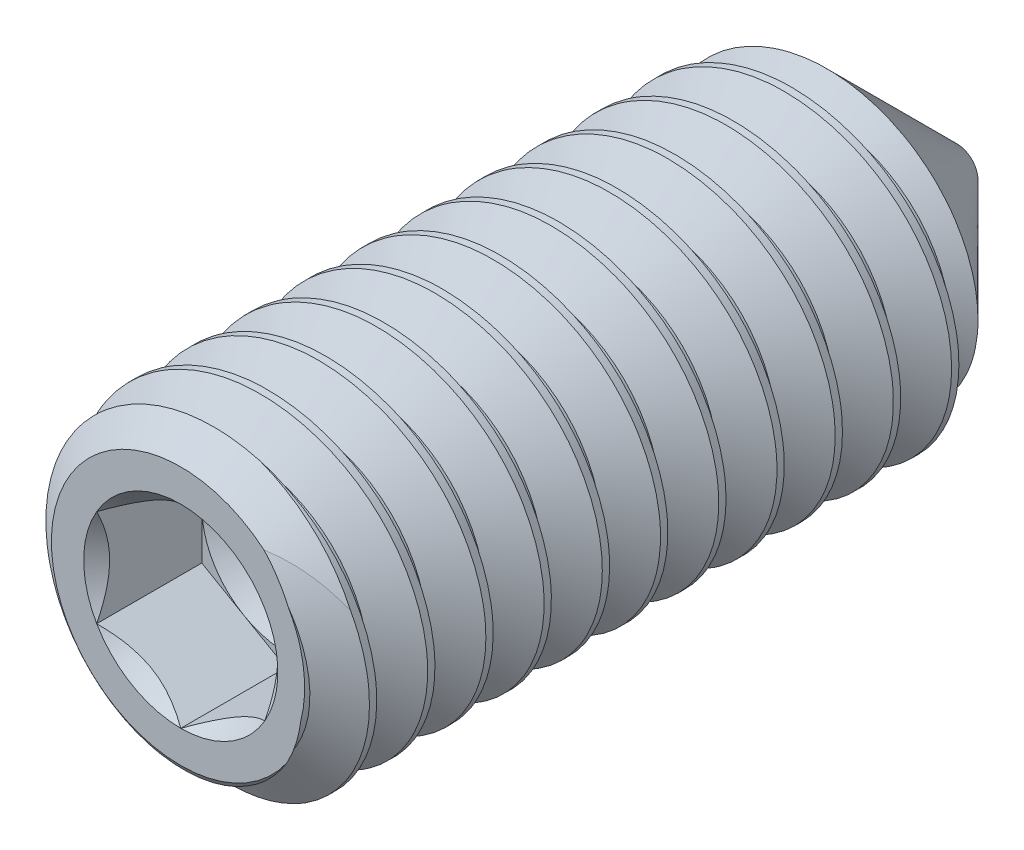
SolidWorks part; units mm, degrees
ref_plane "Front" through (0, 0, 0) normal (0, 0, 1) x (1, 0, 0)
ref_plane "Top" through (0, 0, 0) normal (0, 1, 0) x (1, 0, 0)
ref_plane "Right" through (0, 0, 0) normal (1, 0, 0) x (0, 0, -1)
sketch "Body Sketch" plane through (0, 0, 0) normal (1, 0, 0) x (0, 0, -1)
  line L0 (-3, 0) -> (-3, 1)
  line L1 (-3, 1) -> (-2.8249, 1.25)
  line L2 (-2.8249, 1.25) -> (1.9125, 1.25)
  line L3 (1.9125, 1.25) -> (3, 0.1625)
  line L4 (-3, 1) -> (-3, -1) construction
  line L5 (3, 0) -> (-3, 0)
  line L6 (0, 1.25) -> (0, -1.25) construction
  line L8 (3, 0.1625) -> (3, 0)
  line L9 (-3, -1.25) -> (3, -1.25) construction
  line L10 (3, 0.1625) -> (3, -0.1625) construction
  line L11 (3, -0.1625) -> (1.9125, -1.25) construction
  line L13 (3, 0.1625) -> (2.8375, 0) construction
  line L15 (2.8375, 0) -> (3, -0.1625) construction
  dimension "D3" = 35
  dimension "D7" = 2
  dimension "Diameter" = 2.5
  dimension "Length" = 6
  dimension "D2" = 0.325
  dimension "Cone Angle" = 90
  dimension "D90" = 90
revolve "Body Revolve" add sketch "Body Sketch" angle 360 about L5
ref_plane "Plane1" through (0, 0, -3) normal (0, 0, 1) x (1, 0, 0)
sketch "Spiral Sketch" plane through (0, 0, -3) normal (0, 0, 1) x (1, 0, 0)
  circle A0 centre (0, 0) radius 1.25 construction
  circle A1 centre (0, 0) radius 1.25
sketch "Hex Sketch" plane through (0, 0, 3) normal (0, 0, 1) x (1, 0, 0)
  line L1 (0, 0.7506) -> (-0.65, 0.3753)
  line L2 (-0.65, 0.3753) -> (-0.65, -0.3753)
  line L3 (-0.65, -0.3753) -> (0, -0.7506)
  line L4 (0, -0.7506) -> (0.65, -0.3753)
  line L5 (0.65, -0.3753) -> (0.65, 0.3753)
  line L6 (0.65, 0.3753) -> (0, 0.7506)
  circle A0 centre (0, 0) radius 0.65 construction
  dimension "Hex" = 1.3
extrude "Hex Extrude" cut sketch "Hex Sketch" against normal blind 0.8125
sketch "Hex Entry Sketch" plane through (0, 0, 3) normal (0, 0, 1) x (1, 0, 0)
  circle A0 centre (0, 0) radius 0.7506
extrude "Hex Entry Extrude" cut sketch "Hex Entry Sketch" against normal through all draft 45
sketch "Hex Bottom Sketch" plane through (0, 0, 2.1875) normal (0, 0, 1) x (1, 0, 0)
  circle A0 centre (0, 0) radius 0.65 construction
  circle A1 centre (0, 0) radius 0.65
extrude "Hex Bottom Extrude" cut sketch "Hex Bottom Sketch" against normal through all draft 60
curve "Helix/Spiral" pitch 0.45 height 6.45 radius 1.25 centre (0, 0, -3) axis (0, 0, 1) start towards (0, 1, 0)
sketch "Sketch28" plane through (0, 0, 0) normal (1, 0, 0) x (0, 0, -1)
  line L0 (3, 1.25) -> (3.3938, 1.25)
  line L1 (3.3938, 1.25) -> (3.225, 0.9577)
  line L2 (3.225, 0.9577) -> (3.1688, 0.9577)
  line L3 (3.1688, 0.9577) -> (3, 1.25)
  line L4 (3.0844, 1.1039) -> (3.3094, 1.1039) construction
  line L6 (-2.8249, 1.25) -> (1.9125, 1.25) construction
  line L7 (3, 6.7518) -> (3, -6.7518) construction
  dimension "D1" = 0.0563
  dimension "D3" = 60
  dimension "D2" = 0.225
sweep "Thread Sweep" cut profiles "Sketch28" path "Helix/Spiral"
ref_plane "Contact Plane 1" through (0, 0, 3) normal (0, 0, 1) x (1, 0, 0)
ref_plane "Contact Plane 2" through (0, 0, -3) normal (0, 0, -1) x (-1, 0, 0)
ref_axis "Center Axis 1" through (0, 0, 48.3835) along (0, 0, -1)
equation "\"D7@Body Sketch\" = \"Diameter@Body Sketch\" * .8"
equation "\"D1@Sketch28\" = \"D4@Helix/Spiral\" * .125"
equation "\"D3@Helix/Spiral\" = \"Length@Body Sketch\" + \"D4@Helix/Spiral\""
equation "\"hex Depth@Hex Extrude\" = \"Hex@Hex Sketch\" * .625"
equation "\"D2@Sketch28\" = \"D4@Helix/Spiral\" * .5"
equation "\"D2@Body Sketch\" = \"Diameter@Body Sketch\" * .13"
equation "\"D90@Body Sketch\" = \"Cone Angle@Body Sketch\""
equation "\"Diameter\"= 2.5mm"
equation "\"Thread Pitch\" = 0.45mm"
equation "\"Hex Size\" = 1.3mm"
equation "\"Diameter@Body Sketch\" = \"Diameter\""
equation "\"Hex@Hex Sketch\" = \"Hex Size\""
equation "\"D4@Helix/Spiral\"=\"Thread Pitch\""
